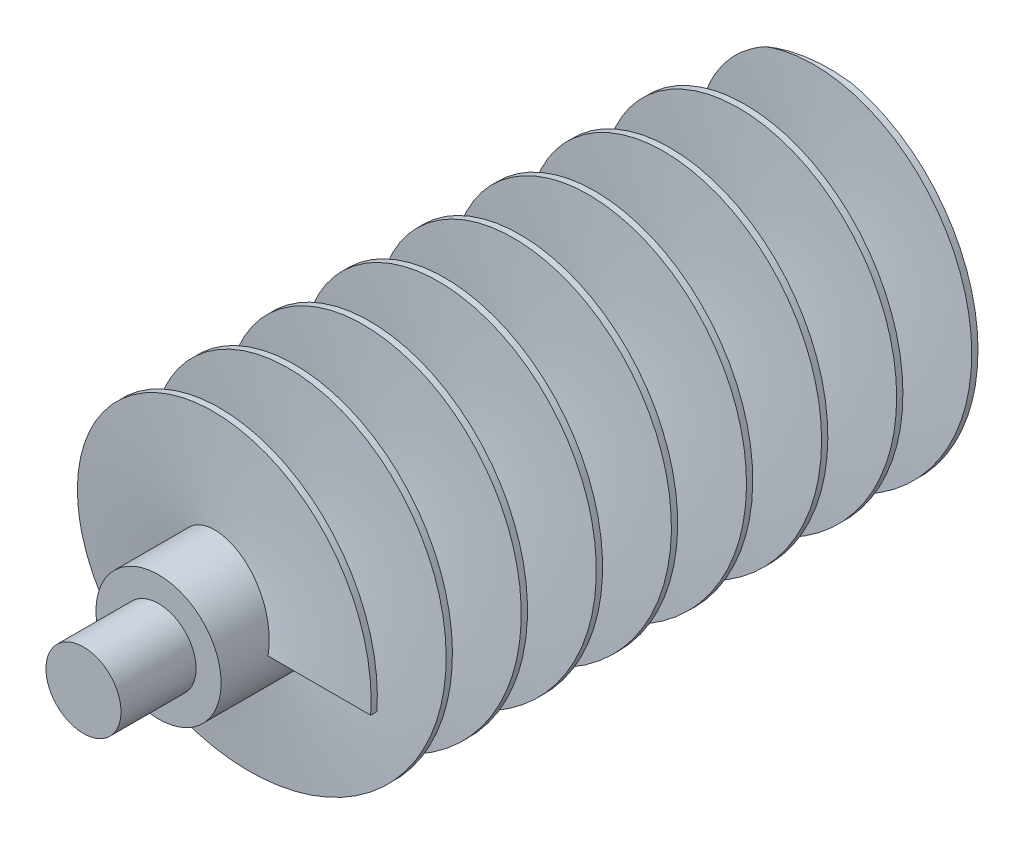
SolidWorks part; units mm, degrees
material "AISI 304"
ref_plane "Спереди" through (0, 0, 0) normal (0, 0, 1) x (1, 0, 0)
ref_plane "Сверху" through (0, 0, 0) normal (0, 1, 0) x (1, 0, 0)
ref_plane "Справа" through (0, 0, 0) normal (1, 0, 0) x (0, 0, -1)
ref_plane "Плоскость1" through (0, 0, -17) normal (0, 0, 1) x (1, 0, 0)
sketch "Эскиз1" plane through (0, 0, 0) normal (0, 0, 1) x (1, 0, 0)
  circle A0 centre (0, 0) radius 15
  dimension "D1" = 30
sketch "Эскиз2" plane through (0, 0, 0) normal (0, 1, 0) x (1, 0, 0)
  line L0 (25, 0) -> (-4.9813, 0) construction
  line L1 (25, 1.25) -> (66, 1.25)
  line L2 (25, 1.25) -> (25, -1.25)
  line L3 (25, -1.25) -> (66, -1.25)
  line L4 (66, 1.25) -> (66, -1.25)
  dimension "D1" = 2.5
  dimension "D2" = 25
  dimension "D3" = 66
curve "Спираль1" pitch 30 height 300 radius 15 left hand yes centre (0, 0, 0) axis (0, 0, -1) start towards (1, 0, 0)
sweep "По траектории1" add profiles "Эскиз2" path "Спираль1"
sketch "Эскиз3" plane through (0, 0, 0) normal (0, 1, 0) x (1, 0, 0)
  line L0 (0, -50) -> (15, -50)
  line L1 (15, -50) -> (15, -20)
  line L2 (15, -20) -> (25, -20)
  line L3 (25, -20) -> (25, 300)
  line L4 (25, 300) -> (0, 300)
  line L5 (0, 300) -> (0, -50)
  line L6 (0, -59.6319) -> (0, 170.3599) construction
  dimension "D1" = 350
  dimension "D2" = 50
  dimension "D3" = 30
  dimension "D4" = 30
revolve "Повернуть1" add sketch "Эскиз3" angle 360 mid plane about L6
sketch "Эскиз4" plane through (0, 0, 0) normal (1, 0, 0) x (0, 0, -1)
  line L0 (274.0415, 0) -> (145.9291, 0) construction
  line L1 (301.25, 0) -> (286.25, 0)
  line L2 (301.25, 0) -> (301.25, -82.7969)
  line L3 (301.25, -82.7969) -> (238.4472, -82.7969)
  line L4 (286.25, 0) -> (238.4472, -82.7969)
  spline S2 degree 2 poles (1.25, 0) (1.9318, 9.4894) (2.6136, 18.5943) (3.2955, 27.6993) (3.9773, 35.6823) (4.6591, 43.6653) (5.3409, 49.8795) (6.0227, 56.0937) (6.7045, 60.0357) (7.3864, 63.9777) (8.0682, 65.3282) (8.75, 66.6787) (9.4318, 65.3282) (10.1136, 63.9777) (10.7955, 60.0357) (11.4773, 56.0937) (12.1591, 49.8795) (12.8409, 43.6653) (13.5227, 35.6823) (14.2045, 27.6993) (14.8864, 18.5943) (15.5682, 9.4894) (16.25, 0) (16.9318, -9.4894) (17.6136, -18.5943) (18.2955, -27.6993) (18.9773, -35.6823) (19.6591, -43.6653) (20.3409, -49.8795) (21.0227, -56.0937) (21.7045, -60.0357) (22.3864, -63.9777) (23.0682, -65.3282) (23.75, -66.6787) (24.4318, -65.3282) (25.1136, -63.9777) (25.7955, -60.0357) (26.4773, -56.0937) (27.1591, -49.8795) (27.8409, -43.6653) (28.5227, -35.6823) (29.2045, -27.6993) (29.8864, -18.5943) (30.5682, -9.4894) (31.25, 0) (31.9318, 9.4894) (32.6136, 18.5943) (33.2955, 27.6993) (33.9773, 35.6823) (34.6591, 43.6653) (35.3409, 49.8795) (36.0227, 56.0937) (36.7045, 60.0357) (37.3864, 63.9777) (38.0682, 65.3282) (38.75, 66.6787) (39.4318, 65.3282) (40.1136, 63.9777) (40.7955, 60.0357) (41.4773, 56.0937) (42.1591, 49.8795) (42.8409, 43.6653) (43.5227, 35.6823) (44.2045, 27.6993) (44.8864, 18.5943) (45.5682, 9.4894) (46.25, 0) (46.9318, -9.4894) (47.6136, -18.5943) (48.2955, -27.6993) (48.9773, -35.6823) (49.6591, -43.6653) (50.3409, -49.8795) (51.0227, -56.0937) (51.7045, -60.0357) (52.3864, -63.9777) (53.0682, -65.3282) (53.75, -66.6787) (54.4318, -65.3282) (55.1136, -63.9777) (55.7955, -60.0357) (56.4773, -56.0937) (57.1591, -49.8795) (57.8409, -43.6653) (58.5227, -35.6823) (59.2045, -27.6993) (59.8864, -18.5943) (60.5682, -9.4894) (61.25, 0) (61.9318, 9.4894) (62.6136, 18.5943) (63.2955, 27.6993) (63.9773, 35.6823) (64.6591, 43.6653) (65.3409, 49.8795) (66.0227, 56.0937) (66.7045, 60.0357) (67.3864, 63.9777) (68.0682, 65.3282) (68.75, 66.6787) (69.4318, 65.3282) (70.1136, 63.9777) (70.7955, 60.0357) (71.4773, 56.0937) (72.1591, 49.8795) (72.8409, 43.6653) (73.5227, 35.6823) (74.2045, 27.6993) (74.8864, 18.5943) (75.5682, 9.4894) (76.25, 0) (76.9318, -9.4894) (77.6136, -18.5943) (78.2955, -27.6993) (78.9773, -35.6823) (79.6591, -43.6653) (80.3409, -49.8795) (81.0227, -56.0937) (81.7045, -60.0357) (82.3864, -63.9777) (83.0682, -65.3282) (83.75, -66.6787) (84.4318, -65.3282) (85.1136, -63.9777) (85.7955, -60.0357) (86.4773, -56.0937) (87.1591, -49.8795) (87.8409, -43.6653) (88.5227, -35.6823) (89.2045, -27.6993) (89.8864, -18.5943) (90.5682, -9.4894) (91.25, 0) (91.9318, 9.4894) (92.6136, 18.5943) (93.2955, 27.6993) (93.9773, 35.6823) (94.6591, 43.6653) (95.3409, 49.8795) (96.0227, 56.0937) (96.7045, 60.0357) (97.3864, 63.9777) (98.0682, 65.3282) (98.75, 66.6787) (99.4318, 65.3282) (100.1136, 63.9777) (100.7955, 60.0357) (101.4773, 56.0937) (102.1591, 49.8795) (102.8409, 43.6653) (103.5227, 35.6823) (104.2045, 27.6993) (104.8864, 18.5943) (105.5682, 9.4894) (106.25, 0) (106.9318, -9.4894) (107.6136, -18.5943) (108.2955, -27.6993) (108.9773, -35.6823) (109.6591, -43.6653) (110.3409, -49.8795) (111.0227, -56.0937) (111.7045, -60.0357) (112.3864, -63.9777) (113.0682, -65.3282) (113.75, -66.6787) (114.4318, -65.3282) (115.1136, -63.9777) (115.7955, -60.0357) (116.4773, -56.0937) (117.1591, -49.8795) (117.8409, -43.6653) (118.5227, -35.6823) (119.2045, -27.6993) (119.8864, -18.5943) (120.5682, -9.4894) (121.25, 0) (121.9318, 9.4894) (122.6136, 18.5943) (123.2955, 27.6993) (123.9773, 35.6823) (124.6591, 43.6653) (125.3409, 49.8795) (126.0227, 56.0937) (126.7045, 60.0357) (127.3864, 63.9777) (128.0682, 65.3282) (128.75, 66.6787) (129.4318, 65.3282) (130.1136, 63.9777) (130.7955, 60.0357) (131.4773, 56.0937) (132.1591, 49.8795) (132.8409, 43.6653) (133.5227, 35.6823) (134.2045, 27.6993) (134.8864, 18.5943) (135.5682, 9.4894) (136.25, 0) (136.9318, -9.4894) (137.6136, -18.5943) (138.2955, -27.6993) (138.9773, -35.6823) (139.6591, -43.6653) (140.3409, -49.8795) (141.0227, -56.0937) (141.7045, -60.0357) (142.3864, -63.9777) (143.0682, -65.3282) (143.75, -66.6787) (144.4318, -65.3282) (145.1136, -63.9777) (145.7955, -60.0357) (146.4773, -56.0937) (147.1591, -49.8795) (147.8409, -43.6653) (148.5227, -35.6823) (149.2045, -27.6993) (149.8864, -18.5943) (150.5682, -9.4894) (151.25, 0) (151.9318, 9.4894) (152.6136, 18.5943) (153.2955, 27.6993) (153.9773, 35.6823) (154.6591, 43.6653) (155.3409, 49.8795) (156.0227, 56.0937) (156.7045, 60.0357) (157.3864, 63.9777) (158.0682, 65.3282) (158.75, 66.6787) (159.4318, 65.3282) (160.1136, 63.9777) (160.7955, 60.0357) (161.4773, 56.0937) (162.1591, 49.8795) (162.8409, 43.6653) (163.5227, 35.6823) (164.2045, 27.6993) (164.8864, 18.5943) (165.5682, 9.4894) (166.25, 0) (166.9318, -9.4894) (167.6136, -18.5943) (168.2955, -27.6993) (168.9773, -35.6823) (169.6591, -43.6653) (170.3409, -49.8795) (171.0227, -56.0937) (171.7045, -60.0357) (172.3864, -63.9777) (173.0682, -65.3282) (173.75, -66.6787) (174.4318, -65.3282) (175.1136, -63.9777) (175.7955, -60.0357) (176.4773, -56.0937) (177.1591, -49.8795) (177.8409, -43.6653) (178.5227, -35.6823) (179.2045, -27.6993) (179.8864, -18.5943) (180.5682, -9.4894) (181.25, 0) (181.9318, 9.4894) (182.6136, 18.5943) (183.2955, 27.6993) (183.9773, 35.6823) (184.6591, 43.6653) (185.3409, 49.8795) (186.0227, 56.0937) (186.7045, 60.0357) (187.3864, 63.9777) (188.0682, 65.3282) (188.75, 66.6787) (189.4318, 65.3282) (190.1136, 63.9777) (190.7955, 60.0357) (191.4773, 56.0937) (192.1591, 49.8795) (192.8409, 43.6653) (193.5227, 35.6823) (194.2045, 27.6993) (194.8864, 18.5943) (195.5682, 9.4894) (196.25, 0) (196.9318, -9.4894) (197.6136, -18.5943) (198.2955, -27.6993) (198.9773, -35.6823) (199.6591, -43.6653) (200.3409, -49.8795) (201.0227, -56.0937) (201.7045, -60.0357) (202.3864, -63.9777) (203.0682, -65.3282) (203.75, -66.6787) (204.4318, -65.3282) (205.1136, -63.9777) (205.7955, -60.0357) (206.4773, -56.0937) (207.1591, -49.8795) (207.8409, -43.6653) (208.5227, -35.6823) (209.2045, -27.6993) (209.8864, -18.5943) (210.5682, -9.4894) (211.25, 0) (211.9318, 9.4894) (212.6136, 18.5943) (213.2955, 27.6993) (213.9773, 35.6823) (214.6591, 43.6653) (215.3409, 49.8795) (216.0227, 56.0937) (216.7045, 60.0357) (217.3864, 63.9777) (218.0682, 65.3282) (218.75, 66.6787) (219.4318, 65.3282) (220.1136, 63.9777) (220.7955, 60.0357) (221.4773, 56.0937) (222.1591, 49.8795) (222.8409, 43.6653) (223.5227, 35.6823) (224.2045, 27.6993) (224.8864, 18.5943) (225.5682, 9.4894) (226.25, 0) (226.9318, -9.4894) (227.6136, -18.5943) (228.2955, -27.6993) (228.9773, -35.6823) (229.6591, -43.6653) (230.3409, -49.8795) (231.0227, -56.0937) (231.7045, -60.0357) (232.3864, -63.9777) (233.0682, -65.3282) (233.75, -66.6787) (234.4318, -65.3282) (235.1136, -63.9777) (235.7955, -60.0357) (236.4773, -56.0937) (237.1591, -49.8795) (237.8409, -43.6653) (238.5227, -35.6823) (239.2045, -27.6993) (239.8864, -18.5943) (240.5682, -9.4894) (241.25, 0) (241.9318, 9.4894) (242.6136, 18.5943) (243.2955, 27.6993) (243.9773, 35.6823) (244.6591, 43.6653) (245.3409, 49.8795) (246.0227, 56.0937) (246.7045, 60.0357) (247.3864, 63.9777) (248.0682, 65.3282) (248.75, 66.6787) (249.4318, 65.3282) (250.1136, 63.9777) (250.7955, 60.0357) (251.4773, 56.0937) (252.1591, 49.8795) (252.8409, 43.6653) (253.5227, 35.6823) (254.2045, 27.6993) (254.8864, 18.5943) (255.5682, 9.4894) (256.25, 0) (256.9318, -9.4894) (257.6136, -18.5943) (258.2955, -27.6993) (258.9773, -35.6823) (259.6591, -43.6653) (260.3409, -49.8795) (261.0227, -56.0937) (261.7045, -60.0357) (262.3864, -63.9777) (263.0682, -65.3282) (263.75, -66.6787) (264.4318, -65.3282) (265.1136, -63.9777) (265.7955, -60.0357) (266.4773, -56.0937) (267.1591, -49.8795) (267.8409, -43.6653) (268.5227, -35.6823) (269.2045, -27.6993) (269.8864, -18.5943) (270.5682, -9.4894) (271.25, 0) (271.9318, 9.4894) (272.6136, 18.5943) (273.2955, 27.6993) (273.9773, 35.6823) (274.6591, 43.6653) (275.3409, 49.8795) (276.0227, 56.0937) (276.7045, 60.0357) (277.3864, 63.9777) (278.0682, 65.3282) (278.75, 66.6787) (279.4318, 65.3282) (280.1136, 63.9777) (280.7955, 60.0357) (281.4773, 56.0937) (282.1591, 49.8795) (282.8409, 43.6653) (283.5227, 35.6823) (284.2045, 27.6993) (284.8864, 18.5943) (285.5682, 9.4894) (286.25, 0) (286.9318, -9.4894) (287.6136, -18.5943) (288.2955, -27.6993) (288.9773, -35.6823) (289.6591, -43.6653) (290.3409, -49.8795) (291.0227, -56.0937) (291.7045, -60.0357) (292.3864, -63.9777) (293.0682, -65.3282) (293.75, -66.6787) (294.4318, -65.3282) (295.1136, -63.9777) (295.7955, -60.0357) (296.4773, -56.0937) (297.1591, -49.8795) (297.8409, -43.6653) (298.5227, -35.6823) (299.2045, -27.6993) (299.8864, -18.5943) (300.5682, -9.4894) (301.25, 0) knots 0 0 0 0.004545 0.004545 0.009091 0.009091 0.013636 0.013636 0.018182 0.018182 0.022727 0.022727 0.027273 0.027273 0.031818 0.031818 0.036364 0.036364 0.040909 0.040909 0.045455 0.045455 0.05 0.05 0.054545 0.054545 0.059091 0.059091 0.063636 0.063636 0.068182 0.068182 0.072727 0.072727 0.077273 0.077273 0.081818 0.081818 0.086364 0.086364 0.090909 0.090909 0.095455 0.095455 0.1 0.1 0.104545 0.104545 0.109091 0.109091 0.113636 0.113636 0.118182 0.118182 0.122727 0.122727 0.127273 0.127273 0.131818 0.131818 0.136364 0.136364 0.140909 0.140909 0.145455 0.145455 0.15 0.15 0.154545 0.154545 0.159091 0.159091 0.163636 0.163636 0.168182 0.168182 0.172727 0.172727 0.177273 0.177273 0.181818 0.181818 0.186364 0.186364 0.190909 0.190909 0.195455 0.195455 0.2 0.2 0.204545 0.204545 0.209091 0.209091 0.213636 0.213636 0.218182 0.218182 0.222727 0.222727 0.227273 0.227273 0.231818 0.231818 0.236364 0.236364 0.240909 0.240909 0.245455 0.245455 0.25 0.25 0.254545 0.254545 0.259091 0.259091 0.263636 0.263636 0.268182 0.268182 0.272727 0.272727 0.277273 0.277273 0.281818 0.281818 0.286364 0.286364 0.290909 0.290909 0.295455 0.295455 0.3 0.3 0.304545 0.304545 0.309091 0.309091 0.313636 0.313636 0.318182 0.318182 0.322727 0.322727 0.327273 0.327273 0.331818 0.331818 0.336364 0.336364 0.340909 0.340909 0.345455 0.345455 0.35 0.35 0.354545 0.354545 0.359091 0.359091 0.363636 0.363636 0.368182 0.368182 0.372727 0.372727 0.377273 0.377273 0.381818 0.381818 0.386364 0.386364 0.390909 0.390909 0.395455 0.395455 0.4 0.4 0.404545 0.404545 0.409091 0.409091 0.413636 0.413636 0.418182 0.418182 0.422727 0.422727 0.427273 0.427273 0.431818 0.431818 0.436364 0.436364 0.440909 0.440909 0.445455 0.445455 0.45 0.45 0.454545 0.454545 0.459091 0.459091 0.463636 0.463636 0.468182 0.468182 0.472727 0.472727 0.477273 0.477273 0.481818 0.481818 0.486364 0.486364 0.490909 0.490909 0.495455 0.495455 0.5 0.5 0.504545 0.504545 0.509091 0.509091 0.513636 0.513636 0.518182 0.518182 0.522727 0.522727 0.527273 0.527273 0.531818 0.531818 0.536364 0.536364 0.540909 0.540909 0.545455 0.545455 0.55 0.55 0.554545 0.554545 0.559091 0.559091 0.563636 0.563636 0.568182 0.568182 0.572727 0.572727 0.577273 0.577273 0.581818 0.581818 0.586364 0.586364 0.590909 0.590909 0.595455 0.595455 0.6 0.6 0.604545 0.604545 0.609091 0.609091 0.613636 0.613636 0.618182 0.618182 0.622727 0.622727 0.627273 0.627273 0.631818 0.631818 0.636364 0.636364 0.640909 0.640909 0.645455 0.645455 0.65 0.65 0.654545 0.654545 0.659091 0.659091 0.663636 0.663636 0.668182 0.668182 0.672727 0.672727 0.677273 0.677273 0.681818 0.681818 0.686364 0.686364 0.690909 0.690909 0.695455 0.695455 0.7 0.7 0.704545 0.704545 0.709091 0.709091 0.713636 0.713636 0.718182 0.718182 0.722727 0.722727 0.727273 0.727273 0.731818 0.731818 0.736364 0.736364 0.740909 0.740909 0.745455 0.745455 0.75 0.75 0.754545 0.754545 0.759091 0.759091 0.763636 0.763636 0.768182 0.768182 0.772727 0.772727 0.777273 0.777273 0.781818 0.781818 0.786364 0.786364 0.790909 0.790909 0.795455 0.795455 0.8 0.8 0.804545 0.804545 0.809091 0.809091 0.813636 0.813636 0.818182 0.818182 0.822727 0.822727 0.827273 0.827273 0.831818 0.831818 0.836364 0.836364 0.840909 0.840909 0.845455 0.845455 0.85 0.85 0.854545 0.854545 0.859091 0.859091 0.863636 0.863636 0.868182 0.868182 0.872727 0.872727 0.877273 0.877273 0.881818 0.881818 0.886364 0.886364 0.890909 0.890909 0.895455 0.895455 0.9 0.9 0.904545 0.904545 0.909091 0.909091 0.913636 0.913636 0.918182 0.918182 0.922727 0.922727 0.927273 0.927273 0.931818 0.931818 0.936364 0.936364 0.940909 0.940909 0.945455 0.945455 0.95 0.95 0.954545 0.954545 0.959091 0.959091 0.963636 0.963636 0.968182 0.968182 0.972727 0.972727 0.977273 0.977273 0.981818 0.981818 0.986364 0.986364 0.990909 0.990909 0.995455 0.995455 1 1 1 weights 1 0.989821 1 0.989821 1 0.989821 1 0.989821 1 0.989821 1 0.989821 1 0.989821 1 0.989821 1 0.989821 1 0.989821 1 0.989821 1 0.989821 1 0.989821 1 0.989821 1 0.989821 1 0.989821 1 0.989821 1 0.989821 1 0.989821 1 0.989821 1 0.989821 1 0.989821 1 0.989821 1 0.989821 1 0.989821 1 0.989821 1 0.989821 1 0.989821 1 0.989821 1 0.989821 1 0.989821 1 0.989821 1 0.989821 1 0.989821 1 0.989821 1 0.989821 1 0.989821 1 0.989821 1 0.989821 1 0.989821 1 0.989821 1 0.989821 1 0.989821 1 0.989821 1 0.989821 1 0.989821 1 0.989821 1 0.989821 1 0.989821 1 0.989821 1 0.989821 1 0.989821 1 0.989821 1 0.989821 1 0.989821 1 0.989821 1 0.989821 1 0.989821 1 0.989821 1 0.989821 1 0.989821 1 0.989821 1 0.989821 1 0.989821 1 0.989821 1 0.989821 1 0.989821 1 0.989821 1 0.989821 1 0.989821 1 0.989821 1 0.989821 1 0.989821 1 0.989821 1 0.989821 1 0.989821 1 0.989821 1 0.989821 1 0.989821 1 0.989821 1 0.989821 1 0.989821 1 0.989821 1 0.989821 1 0.989821 1 0.989821 1 0.989821 1 0.989821 1 0.989821 1 0.989821 1 0.989821 1 0.989821 1 0.989821 1 0.989821 1 0.989821 1 0.989821 1 0.989821 1 0.989821 1 0.989821 1 0.989821 1 0.989821 1 0.989821 1 0.989821 1 0.989821 1 0.989821 1 0.989821 1 0.989821 1 0.989821 1 0.989821 1 0.989821 1 0.989821 1 0.989821 1 0.989821 1 0.989821 1 0.989821 1 0.989821 1 0.989821 1 0.989821 1 0.989821 1 0.989821 1 0.989821 1 0.989821 1 0.989821 1 0.989821 1 0.989821 1 0.989821 1 0.989821 1 0.989821 1 0.989821 1 0.989821 1 0.989821 1 0.989821 1 0.989821 1 0.989821 1 0.989821 1 0.989821 1 0.989821 1 0.989821 1 0.989821 1 0.989821 1 0.989821 1 0.989821 1 0.989821 1 0.989821 1 0.989821 1 0.989821 1 0.989821 1 0.989821 1 0.989821 1 0.989821 1 0.989821 1 0.989821 1 0.989821 1 0.989821 1 0.989821 1 0.989821 1 0.989821 1 0.989821 1 0.989821 1 0.989821 1 0.989821 1 0.989821 1 0.989821 1 0.989821 1 0.989821 1 0.989821 1 0.989821 1 0.989821 1 0.989821 1 0.989821 1 0.989821 1 0.989821 1 0.989821 1 0.989821 1 0.989821 1 0.989821 1 0.989821 1 0.989821 1 0.989821 1 0.989821 1 0.989821 1 0.989821 1 0.989821 1 0.989821 1 0.989821 1 0.989821 1 0.989821 1 0.989821 1 0.989821 1 0.989821 1 0.989821 1 0.989821 1 0.989821 1 0.989821 1 0.989821 1 0.989821 1 0.989821 1 0.989821 1 0.989821 1 0.989821 1 0.989821 1 0.989821 1 0.989821 1 0.989821 1 0.989821 1 0.989821 1 0.989821 1 0.989821 1 0.989821 1 0.989821 1 0.989821 1 0.989821 1 0.989821 1 0.989821 1 0.989821 1 0.989821 1 0.989821 1 0.989821 1 0.989821 1 0.989821 1 construction
  spline S3 degree 2 poles (1.25, 0) (1.9318, 3.5945) (2.6136, 7.0433) (3.2955, 10.4922) (3.9773, 13.516) (4.6591, 16.5399) (5.3409, 18.8937) (6.0227, 21.2476) (6.7045, 22.7408) (7.3864, 24.234) (8.0682, 24.7455) (8.75, 25.2571) (9.4318, 24.7455) (10.1136, 24.234) (10.7955, 22.7408) (11.4773, 21.2476) (12.1591, 18.8937) (12.8409, 16.5399) (13.5227, 13.516) (14.2045, 10.4922) (14.8864, 7.0433) (15.5682, 3.5945) (16.25, 0) (16.9318, -3.5945) (17.6136, -7.0433) (18.2955, -10.4922) (18.9773, -13.516) (19.6591, -16.5399) (20.3409, -18.8937) (21.0227, -21.2476) (21.7045, -22.7408) (22.3864, -24.234) (23.0682, -24.7455) (23.75, -25.2571) (24.4318, -24.7455) (25.1136, -24.234) (25.7955, -22.7408) (26.4773, -21.2476) (27.1591, -18.8937) (27.8409, -16.5399) (28.5227, -13.516) (29.2045, -10.4922) (29.8864, -7.0433) (30.5682, -3.5945) (31.25, 0) (31.9318, 3.5945) (32.6136, 7.0433) (33.2955, 10.4922) (33.9773, 13.516) (34.6591, 16.5399) (35.3409, 18.8937) (36.0227, 21.2476) (36.7045, 22.7408) (37.3864, 24.234) (38.0682, 24.7455) (38.75, 25.2571) (39.4318, 24.7455) (40.1136, 24.234) (40.7955, 22.7408) (41.4773, 21.2476) (42.1591, 18.8937) (42.8409, 16.5399) (43.5227, 13.516) (44.2045, 10.4922) (44.8864, 7.0433) (45.5682, 3.5945) (46.25, 0) (46.9318, -3.5945) (47.6136, -7.0433) (48.2955, -10.4922) (48.9773, -13.516) (49.6591, -16.5399) (50.3409, -18.8937) (51.0227, -21.2476) (51.7045, -22.7408) (52.3864, -24.234) (53.0682, -24.7455) (53.75, -25.2571) (54.4318, -24.7455) (55.1136, -24.234) (55.7955, -22.7408) (56.4773, -21.2476) (57.1591, -18.8937) (57.8409, -16.5399) (58.5227, -13.516) (59.2045, -10.4922) (59.8864, -7.0433) (60.5682, -3.5945) (61.25, 0) (61.9318, 3.5945) (62.6136, 7.0433) (63.2955, 10.4922) (63.9773, 13.516) (64.6591, 16.5399) (65.3409, 18.8937) (66.0227, 21.2476) (66.7045, 22.7408) (67.3864, 24.234) (68.0682, 24.7455) (68.75, 25.2571) (69.4318, 24.7455) (70.1136, 24.234) (70.7955, 22.7408) (71.4773, 21.2476) (72.1591, 18.8937) (72.8409, 16.5399) (73.5227, 13.516) (74.2045, 10.4922) (74.8864, 7.0433) (75.5682, 3.5945) (76.25, 0) (76.9318, -3.5945) (77.6136, -7.0433) (78.2955, -10.4922) (78.9773, -13.516) (79.6591, -16.5399) (80.3409, -18.8937) (81.0227, -21.2476) (81.7045, -22.7408) (82.3864, -24.234) (83.0682, -24.7455) (83.75, -25.2571) (84.4318, -24.7455) (85.1136, -24.234) (85.7955, -22.7408) (86.4773, -21.2476) (87.1591, -18.8937) (87.8409, -16.5399) (88.5227, -13.516) (89.2045, -10.4922) (89.8864, -7.0433) (90.5682, -3.5945) (91.25, 0) (91.9318, 3.5945) (92.6136, 7.0433) (93.2955, 10.4922) (93.9773, 13.516) (94.6591, 16.5399) (95.3409, 18.8937) (96.0227, 21.2476) (96.7045, 22.7408) (97.3864, 24.234) (98.0682, 24.7455) (98.75, 25.2571) (99.4318, 24.7455) (100.1136, 24.234) (100.7955, 22.7408) (101.4773, 21.2476) (102.1591, 18.8937) (102.8409, 16.5399) (103.5227, 13.516) (104.2045, 10.4922) (104.8864, 7.0433) (105.5682, 3.5945) (106.25, 0) (106.9318, -3.5945) (107.6136, -7.0433) (108.2955, -10.4922) (108.9773, -13.516) (109.6591, -16.5399) (110.3409, -18.8937) (111.0227, -21.2476) (111.7045, -22.7408) (112.3864, -24.234) (113.0682, -24.7455) (113.75, -25.2571) (114.4318, -24.7455) (115.1136, -24.234) (115.7955, -22.7408) (116.4773, -21.2476) (117.1591, -18.8937) (117.8409, -16.5399) (118.5227, -13.516) (119.2045, -10.4922) (119.8864, -7.0433) (120.5682, -3.5945) (121.25, 0) (121.9318, 3.5945) (122.6136, 7.0433) (123.2955, 10.4922) (123.9773, 13.516) (124.6591, 16.5399) (125.3409, 18.8937) (126.0227, 21.2476) (126.7045, 22.7408) (127.3864, 24.234) (128.0682, 24.7455) (128.75, 25.2571) (129.4318, 24.7455) (130.1136, 24.234) (130.7955, 22.7408) (131.4773, 21.2476) (132.1591, 18.8937) (132.8409, 16.5399) (133.5227, 13.516) (134.2045, 10.4922) (134.8864, 7.0433) (135.5682, 3.5945) (136.25, 0) (136.9318, -3.5945) (137.6136, -7.0433) (138.2955, -10.4922) (138.9773, -13.516) (139.6591, -16.5399) (140.3409, -18.8937) (141.0227, -21.2476) (141.7045, -22.7408) (142.3864, -24.234) (143.0682, -24.7455) (143.75, -25.2571) (144.4318, -24.7455) (145.1136, -24.234) (145.7955, -22.7408) (146.4773, -21.2476) (147.1591, -18.8937) (147.8409, -16.5399) (148.5227, -13.516) (149.2045, -10.4922) (149.8864, -7.0433) (150.5682, -3.5945) (151.25, 0) (151.9318, 3.5945) (152.6136, 7.0433) (153.2955, 10.4922) (153.9773, 13.516) (154.6591, 16.5399) (155.3409, 18.8937) (156.0227, 21.2476) (156.7045, 22.7408) (157.3864, 24.234) (158.0682, 24.7455) (158.75, 25.2571) (159.4318, 24.7455) (160.1136, 24.234) (160.7955, 22.7408) (161.4773, 21.2476) (162.1591, 18.8937) (162.8409, 16.5399) (163.5227, 13.516) (164.2045, 10.4922) (164.8864, 7.0433) (165.5682, 3.5945) (166.25, 0) (166.9318, -3.5945) (167.6136, -7.0433) (168.2955, -10.4922) (168.9773, -13.516) (169.6591, -16.5399) (170.3409, -18.8937) (171.0227, -21.2476) (171.7045, -22.7408) (172.3864, -24.234) (173.0682, -24.7455) (173.75, -25.2571) (174.4318, -24.7455) (175.1136, -24.234) (175.7955, -22.7408) (176.4773, -21.2476) (177.1591, -18.8937) (177.8409, -16.5399) (178.5227, -13.516) (179.2045, -10.4922) (179.8864, -7.0433) (180.5682, -3.5945) (181.25, 0) (181.9318, 3.5945) (182.6136, 7.0433) (183.2955, 10.4922) (183.9773, 13.516) (184.6591, 16.5399) (185.3409, 18.8937) (186.0227, 21.2476) (186.7045, 22.7408) (187.3864, 24.234) (188.0682, 24.7455) (188.75, 25.2571) (189.4318, 24.7455) (190.1136, 24.234) (190.7955, 22.7408) (191.4773, 21.2476) (192.1591, 18.8937) (192.8409, 16.5399) (193.5227, 13.516) (194.2045, 10.4922) (194.8864, 7.0433) (195.5682, 3.5945) (196.25, 0) (196.9318, -3.5945) (197.6136, -7.0433) (198.2955, -10.4922) (198.9773, -13.516) (199.6591, -16.5399) (200.3409, -18.8937) (201.0227, -21.2476) (201.7045, -22.7408) (202.3864, -24.234) (203.0682, -24.7455) (203.75, -25.2571) (204.4318, -24.7455) (205.1136, -24.234) (205.7955, -22.7408) (206.4773, -21.2476) (207.1591, -18.8937) (207.8409, -16.5399) (208.5227, -13.516) (209.2045, -10.4922) (209.8864, -7.0433) (210.5682, -3.5945) (211.25, 0) (211.9318, 3.5945) (212.6136, 7.0433) (213.2955, 10.4922) (213.9773, 13.516) (214.6591, 16.5399) (215.3409, 18.8937) (216.0227, 21.2476) (216.7045, 22.7408) (217.3864, 24.234) (218.0682, 24.7455) (218.75, 25.2571) (219.4318, 24.7455) (220.1136, 24.234) (220.7955, 22.7408) (221.4773, 21.2476) (222.1591, 18.8937) (222.8409, 16.5399) (223.5227, 13.516) (224.2045, 10.4922) (224.8864, 7.0433) (225.5682, 3.5945) (226.25, 0) (226.9318, -3.5945) (227.6136, -7.0433) (228.2955, -10.4922) (228.9773, -13.516) (229.6591, -16.5399) (230.3409, -18.8937) (231.0227, -21.2476) (231.7045, -22.7408) (232.3864, -24.234) (233.0682, -24.7455) (233.75, -25.2571) (234.4318, -24.7455) (235.1136, -24.234) (235.7955, -22.7408) (236.4773, -21.2476) (237.1591, -18.8937) (237.8409, -16.5399) (238.5227, -13.516) (239.2045, -10.4922) (239.8864, -7.0433) (240.5682, -3.5945) (241.25, 0) (241.9318, 3.5945) (242.6136, 7.0433) (243.2955, 10.4922) (243.9773, 13.516) (244.6591, 16.5399) (245.3409, 18.8937) (246.0227, 21.2476) (246.7045, 22.7408) (247.3864, 24.234) (248.0682, 24.7455) (248.75, 25.2571) (249.4318, 24.7455) (250.1136, 24.234) (250.7955, 22.7408) (251.4773, 21.2476) (252.1591, 18.8937) (252.8409, 16.5399) (253.5227, 13.516) (254.2045, 10.4922) (254.8864, 7.0433) (255.5682, 3.5945) (256.25, 0) (256.9318, -3.5945) (257.6136, -7.0433) (258.2955, -10.4922) (258.9773, -13.516) (259.6591, -16.5399) (260.3409, -18.8937) (261.0227, -21.2476) (261.7045, -22.7408) (262.3864, -24.234) (263.0682, -24.7455) (263.75, -25.2571) (264.4318, -24.7455) (265.1136, -24.234) (265.7955, -22.7408) (266.4773, -21.2476) (267.1591, -18.8937) (267.8409, -16.5399) (268.5227, -13.516) (269.2045, -10.4922) (269.8864, -7.0433) (270.5682, -3.5945) (271.25, 0) (271.9318, 3.5945) (272.6136, 7.0433) (273.2955, 10.4922) (273.9773, 13.516) (274.6591, 16.5399) (275.3409, 18.8937) (276.0227, 21.2476) (276.7045, 22.7408) (277.3864, 24.234) (278.0682, 24.7455) (278.75, 25.2571) (279.4318, 24.7455) (280.1136, 24.234) (280.7955, 22.7408) (281.4773, 21.2476) (282.1591, 18.8937) (282.8409, 16.5399) (283.5227, 13.516) (284.2045, 10.4922) (284.8864, 7.0433) (285.5682, 3.5945) (286.25, 0) (286.9318, -3.5945) (287.6136, -7.0433) (288.2955, -10.4922) (288.9773, -13.516) (289.6591, -16.5399) (290.3409, -18.8937) (291.0227, -21.2476) (291.7045, -22.7408) (292.3864, -24.234) (293.0682, -24.7455) (293.75, -25.2571) (294.4318, -24.7455) (295.1136, -24.234) (295.7955, -22.7408) (296.4773, -21.2476) (297.1591, -18.8937) (297.8409, -16.5399) (298.5227, -13.516) (299.2045, -10.4922) (299.8864, -7.0433) (299.9431, -6.7564) (300, -6.4675) knots 0 0 0 0.004545 0.004545 0.009091 0.009091 0.013636 0.013636 0.018182 0.018182 0.022727 0.022727 0.027273 0.027273 0.031818 0.031818 0.036364 0.036364 0.040909 0.040909 0.045455 0.045455 0.05 0.05 0.054545 0.054545 0.059091 0.059091 0.063636 0.063636 0.068182 0.068182 0.072727 0.072727 0.077273 0.077273 0.081818 0.081818 0.086364 0.086364 0.090909 0.090909 0.095455 0.095455 0.1 0.1 0.104545 0.104545 0.109091 0.109091 0.113636 0.113636 0.118182 0.118182 0.122727 0.122727 0.127273 0.127273 0.131818 0.131818 0.136364 0.136364 0.140909 0.140909 0.145455 0.145455 0.15 0.15 0.154545 0.154545 0.159091 0.159091 0.163636 0.163636 0.168182 0.168182 0.172727 0.172727 0.177273 0.177273 0.181818 0.181818 0.186364 0.186364 0.190909 0.190909 0.195455 0.195455 0.2 0.2 0.204545 0.204545 0.209091 0.209091 0.213636 0.213636 0.218182 0.218182 0.222727 0.222727 0.227273 0.227273 0.231818 0.231818 0.236364 0.236364 0.240909 0.240909 0.245455 0.245455 0.25 0.25 0.254545 0.254545 0.259091 0.259091 0.263636 0.263636 0.268182 0.268182 0.272727 0.272727 0.277273 0.277273 0.281818 0.281818 0.286364 0.286364 0.290909 0.290909 0.295455 0.295455 0.3 0.3 0.304545 0.304545 0.309091 0.309091 0.313636 0.313636 0.318182 0.318182 0.322727 0.322727 0.327273 0.327273 0.331818 0.331818 0.336364 0.336364 0.340909 0.340909 0.345455 0.345455 0.35 0.35 0.354545 0.354545 0.359091 0.359091 0.363636 0.363636 0.368182 0.368182 0.372727 0.372727 0.377273 0.377273 0.381818 0.381818 0.386364 0.386364 0.390909 0.390909 0.395455 0.395455 0.4 0.4 0.404545 0.404545 0.409091 0.409091 0.413636 0.413636 0.418182 0.418182 0.422727 0.422727 0.427273 0.427273 0.431818 0.431818 0.436364 0.436364 0.440909 0.440909 0.445455 0.445455 0.45 0.45 0.454545 0.454545 0.459091 0.459091 0.463636 0.463636 0.468182 0.468182 0.472727 0.472727 0.477273 0.477273 0.481818 0.481818 0.486364 0.486364 0.490909 0.490909 0.495455 0.495455 0.5 0.5 0.504545 0.504545 0.509091 0.509091 0.513636 0.513636 0.518182 0.518182 0.522727 0.522727 0.527273 0.527273 0.531818 0.531818 0.536364 0.536364 0.540909 0.540909 0.545455 0.545455 0.55 0.55 0.554545 0.554545 0.559091 0.559091 0.563636 0.563636 0.568182 0.568182 0.572727 0.572727 0.577273 0.577273 0.581818 0.581818 0.586364 0.586364 0.590909 0.590909 0.595455 0.595455 0.6 0.6 0.604545 0.604545 0.609091 0.609091 0.613636 0.613636 0.618182 0.618182 0.622727 0.622727 0.627273 0.627273 0.631818 0.631818 0.636364 0.636364 0.640909 0.640909 0.645455 0.645455 0.65 0.65 0.654545 0.654545 0.659091 0.659091 0.663636 0.663636 0.668182 0.668182 0.672727 0.672727 0.677273 0.677273 0.681818 0.681818 0.686364 0.686364 0.690909 0.690909 0.695455 0.695455 0.7 0.7 0.704545 0.704545 0.709091 0.709091 0.713636 0.713636 0.718182 0.718182 0.722727 0.722727 0.727273 0.727273 0.731818 0.731818 0.736364 0.736364 0.740909 0.740909 0.745455 0.745455 0.75 0.75 0.754545 0.754545 0.759091 0.759091 0.763636 0.763636 0.768182 0.768182 0.772727 0.772727 0.777273 0.777273 0.781818 0.781818 0.786364 0.786364 0.790909 0.790909 0.795455 0.795455 0.8 0.8 0.804545 0.804545 0.809091 0.809091 0.813636 0.813636 0.818182 0.818182 0.822727 0.822727 0.827273 0.827273 0.831818 0.831818 0.836364 0.836364 0.840909 0.840909 0.845455 0.845455 0.85 0.85 0.854545 0.854545 0.859091 0.859091 0.863636 0.863636 0.868182 0.868182 0.872727 0.872727 0.877273 0.877273 0.881818 0.881818 0.886364 0.886364 0.890909 0.890909 0.895455 0.895455 0.9 0.9 0.904545 0.904545 0.909091 0.909091 0.913636 0.913636 0.918182 0.918182 0.922727 0.922727 0.927273 0.927273 0.931818 0.931818 0.936364 0.936364 0.940909 0.940909 0.945455 0.945455 0.95 0.95 0.954545 0.954545 0.959091 0.959091 0.963636 0.963636 0.968182 0.968182 0.972727 0.972727 0.977273 0.977273 0.981818 0.981818 0.986364 0.986364 0.990909 0.990909 0.995455 0.995455 0.995836 0.995836 0.995836 weights 1 0.989821 1 0.989821 1 0.989821 1 0.989821 1 0.989821 1 0.989821 1 0.989821 1 0.989821 1 0.989821 1 0.989821 1 0.989821 1 0.989821 1 0.989821 1 0.989821 1 0.989821 1 0.989821 1 0.989821 1 0.989821 1 0.989821 1 0.989821 1 0.989821 1 0.989821 1 0.989821 1 0.989821 1 0.989821 1 0.989821 1 0.989821 1 0.989821 1 0.989821 1 0.989821 1 0.989821 1 0.989821 1 0.989821 1 0.989821 1 0.989821 1 0.989821 1 0.989821 1 0.989821 1 0.989821 1 0.989821 1 0.989821 1 0.989821 1 0.989821 1 0.989821 1 0.989821 1 0.989821 1 0.989821 1 0.989821 1 0.989821 1 0.989821 1 0.989821 1 0.989821 1 0.989821 1 0.989821 1 0.989821 1 0.989821 1 0.989821 1 0.989821 1 0.989821 1 0.989821 1 0.989821 1 0.989821 1 0.989821 1 0.989821 1 0.989821 1 0.989821 1 0.989821 1 0.989821 1 0.989821 1 0.989821 1 0.989821 1 0.989821 1 0.989821 1 0.989821 1 0.989821 1 0.989821 1 0.989821 1 0.989821 1 0.989821 1 0.989821 1 0.989821 1 0.989821 1 0.989821 1 0.989821 1 0.989821 1 0.989821 1 0.989821 1 0.989821 1 0.989821 1 0.989821 1 0.989821 1 0.989821 1 0.989821 1 0.989821 1 0.989821 1 0.989821 1 0.989821 1 0.989821 1 0.989821 1 0.989821 1 0.989821 1 0.989821 1 0.989821 1 0.989821 1 0.989821 1 0.989821 1 0.989821 1 0.989821 1 0.989821 1 0.989821 1 0.989821 1 0.989821 1 0.989821 1 0.989821 1 0.989821 1 0.989821 1 0.989821 1 0.989821 1 0.989821 1 0.989821 1 0.989821 1 0.989821 1 0.989821 1 0.989821 1 0.989821 1 0.989821 1 0.989821 1 0.989821 1 0.989821 1 0.989821 1 0.989821 1 0.989821 1 0.989821 1 0.989821 1 0.989821 1 0.989821 1 0.989821 1 0.989821 1 0.989821 1 0.989821 1 0.989821 1 0.989821 1 0.989821 1 0.989821 1 0.989821 1 0.989821 1 0.989821 1 0.989821 1 0.989821 1 0.989821 1 0.989821 1 0.989821 1 0.989821 1 0.989821 1 0.989821 1 0.989821 1 0.989821 1 0.989821 1 0.989821 1 0.989821 1 0.989821 1 0.989821 1 0.989821 1 0.989821 1 0.989821 1 0.989821 1 0.989821 1 0.989821 1 0.989821 1 0.989821 1 0.989821 1 0.989821 1 0.989821 1 0.989821 1 0.989821 1 0.989821 1 0.989821 1 0.989821 1 0.989821 1 0.989821 1 0.989821 1 0.989821 1 0.989821 1 0.989821 1 0.989821 1 0.989821 1 0.989821 1 0.989821 1 0.989821 1 0.989821 1 0.989821 1 0.989821 1 0.989821 1 0.989821 1 0.989821 1 0.989821 1 0.989821 1 0.989821 1 0.989821 1 0.989821 1 0.989821 1 0.989821 1 0.989821 1 0.989821 1 0.989821 1 0.989821 1 0.989821 1 0.989821 1 0.989821 1 0.989821 1 0.989821 1 0.989821 1 0.989821 1 0.989821 1 0.989821 1 0.989821 1 0.989821 1 0.989821 1 0.989821 1 0.999145 0.998434 construction
  point P4 (300, 0)
  point P7 (301.25, 0)
  point P11 (215.9472, -69.8065)
  point P12 (0, 0)
  dimension "D1" = 60
revolve "Вырез-Повернуть1" cut sketch "Эскиз4" angle 360 mid plane about L0
